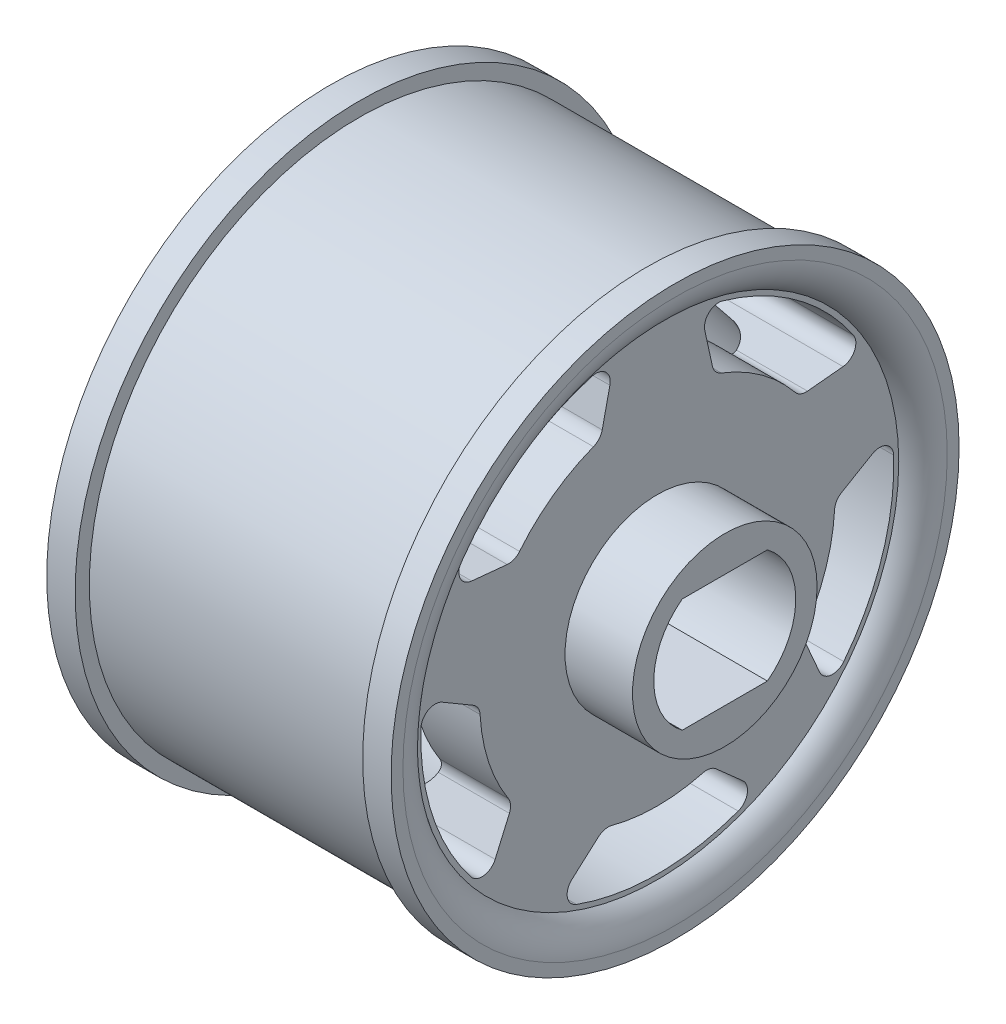
SolidWorks part; units mm, degrees
material "Delrin 2700 NC010, Low Viscosity Acetal Copolymer (SS)"
ref_plane "Front Plane" through (0, 0, 0) normal (0, 0, 1) x (1, 0, 0)
ref_plane "Top Plane" through (0, 0, 0) normal (0, 1, 0) x (1, 0, 0)
ref_plane "Right Plane" through (0, 0, 0) normal (1, 0, 0) x (0, 0, -1)
sketch "Sketch1" plane through (0, 0, 0) normal (0, 1, 0) x (1, 0, 0)
  line L0 (0, 0) -> (0, 6.5)
  line L1 (0, 6.5) -> (-4.75, 6.5)
  line L2 (-4.75, 6.5) -> (-4.75, 17)
  line L3 (0, 0) -> (-9.5, 0)
  line L4 (-9.5, 0) -> (-9.5, 14)
  line L5 (-4.75, 17) -> (-3.5, 17)
  line L6 (-3.5, 17) -> (-3.5, 20)
  line L7 (-3.5, 20) -> (-5.5, 20)
  line L8 (-5.5, 20) -> (-5.5, 19)
  line L9 (-5.5, 19) -> (-25.75, 19)
  line L10 (-25.75, 19) -> (-25.75, 20)
  line L11 (-25.75, 20) -> (-27.75, 20)
  line L12 (-27.75, 20) -> (-27.75, 17)
  line L13 (-9.5, 14) -> (-27.75, 17)
  dimension "D1" = 6.5
  dimension "D2" = 9.5
  dimension "D3" = 4.75
  dimension "D4" = 3.5
  dimension "D5" = 2
  dimension "D6" = 1
  dimension "D7" = 24.25
  dimension "D8" = 20
  dimension "D9" = 17
  dimension "D10" = 14
revolve "Revolve1" add sketch "Sketch1" angle 360 about L3
fillet "Fillet1" radius 2.5 3 edges at (-9.5, 0, -14) (-3.5, 0, -17) (-27.75, 0, -17)
sketch "Sketch2" plane through (0, 0, 0) normal (1, 0, 0) x (0, 0, -1)
  line L1 (-3, -4) -> (3, -4)
  line L2 (-3, -4) -> (-3, 4)
  line L3 (-3, 4) -> (3, 4)
  line L4 (3, -4) -> (3, 4)
  line L5 (-3, -4) -> (3, 4) construction
  line L6 (-3, 4) -> (3, -4) construction
  circle A0 centre (0, 0) radius 5
  circle M1 centre (0, 0) radius 6.5
  dimension "D1" = 10
  dimension "D2" = 8
extrude "Cut-Extrude1" cut sketch "Sketch2" against normal through all contours L2 M1 | L1 L4 L3 L2 | L4 M1 region at (0, 0, 0) region at (0, 0, 3.8155) region at (0, 0, -3.8155)
sketch "Sketch3" plane through (-9.5, 0, 0) normal (-1, 0, 0) x (0, 0, 1)
  line L0 (0, 0) -> (0, 16.6557) construction
  line L1 (-3, 16.3833) -> (-4, 11.8427)
  line L2 (3, 16.3833) -> (4, 11.8427)
  line L3 (14.6544, 7.9159) -> (10.027, 7.4638)
  line L4 (16.5085, 2.2095) -> (12.4992, -0.1446)
  line L5 (12.0569, -11.491) -> (10.197, -7.2298)
  line L6 (7.2028, -15.0177) -> (3.7249, -11.9321)
  line L7 (-7.2028, -15.0177) -> (-3.7249, -11.9321)
  line L8 (-12.0569, -11.491) -> (-10.197, -7.2298)
  line L9 (-16.5085, 2.2095) -> (-12.4992, -0.1446)
  line L10 (-14.6544, 7.9159) -> (-10.027, 7.4638)
  circle A0 centre (0, 0) radius 12.5
  circle A1 centre (0, 0) radius 16.6557 construction
  circle A2 centre (0, 0) radius 16.6557
  point P29 (0, 0)
  dimension "D1" = 25
  dimension "D2" = 3
  dimension "D3" = 3
  dimension "D4" = 4
  dimension "D5" = 5
extrude "Cut-Extrude2" cut sketch "Sketch3" against normal through all and the other way through all contours L1 A2 L10 A0 | L3 A2 L2 A0 | L9 A2 L8 A0 | L7 A2 L6 A0 | L5 A2 L4 A0 region at (-9.5, 11.6663, -8.476) region at (-9.5, 11.6663, 8.476) region at (-9.5, -4.4561, -13.7145) region at (-9.5, -4.4561, 13.7145) region at (-9.5, -14.4203, 0)
fillet "Fillet2" radius 1 20 edges at (-7.1644, -0.1446, 12.4992) (-15.2028, 2.2095, 16.5085) (-15.2028, -11.491, 12.0569) (-7.1644, -7.2298, 10.197) (-7.1644, -7.2298, -10.197) (-15.2028, -11.491, -12.0569) (-7.1644, -0.1446, -12.4992) (-7.1644, 7.4638, -10.027) (-15.2028, 7.9159, -14.6544) (-15.2028, 16.3833, -3) (-7.1644, 11.8427, -4) (-7.1644, 11.8427, 4) (-15.2028, 16.3833, 3) (-15.2028, 7.9159, 14.6544) (-7.1644, 7.4638, 10.027) (-7.1644, -11.9321, 3.7249) (-15.2028, -15.0177, 7.2028) (-15.2028, -15.0177, -7.2028) (-7.1644, -11.9321, -3.7249) (-15.2028, 2.2095, -16.5085)
equation "\"e\"=4.82414"
